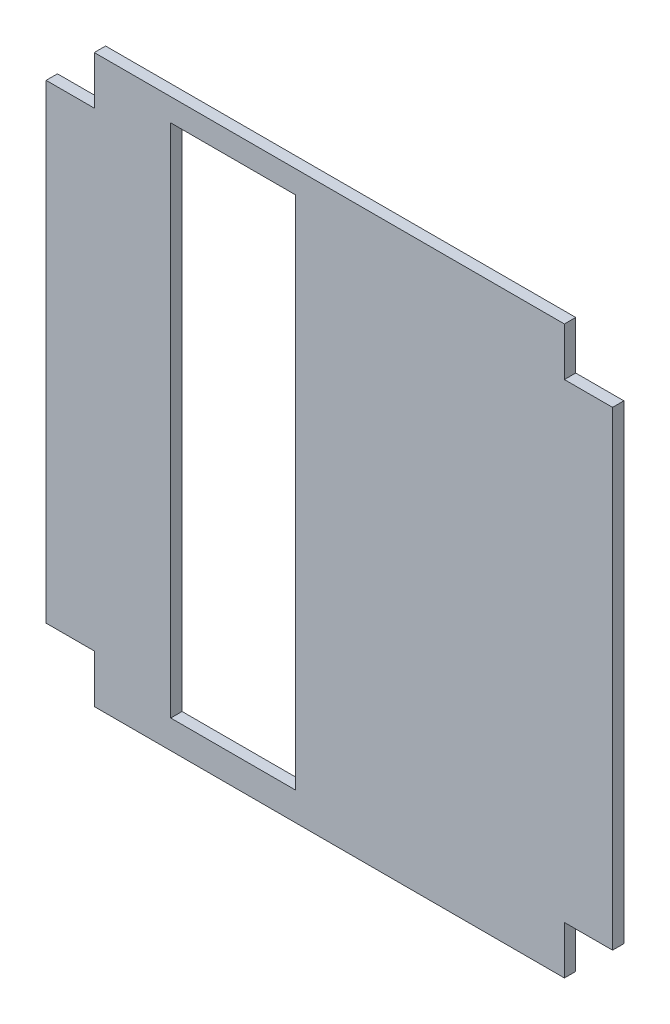
SolidWorks part; units mm, degrees
ref_plane "Front Plane" through (0, 0, 0) normal (0, 0, 1) x (1, 0, 0)
ref_plane "Top Plane" through (0, 0, 0) normal (0, 1, 0) x (1, 0, 0)
ref_plane "Right Plane" through (0, 0, 0) normal (1, 0, 0) x (0, 0, -1)
sketch "Sketch1" plane through (0, 0, 0) normal (0, 0, 1) x (1, 0, 0)
  line L55 (-99, 90.5) -> (-99, 7.5)
  line L58 (-7.5, 99) -> (-90.5, 99)
  line L61 (1, 90.5) -> (1, 7.5)
  line L64 (-90.5, -1) -> (-7.5, -1)
  line L90 (-7.5, 99) -> (-7.5, 90.5)
  line L91 (-7.5, 90.5) -> (1, 90.5)
  line L97 (-90.5, 90.5) -> (-90.5, 99)
  line L98 (-99, 90.5) -> (-90.5, 90.5)
  line L104 (-90.5, 7.5) -> (-99, 7.5)
  line L105 (-90.5, -1) -> (-90.5, 7.5)
  line L107 (-7.5, 7.5) -> (-7.5, -1)
  line L110 (1, 7.5) -> (-7.5, 7.5)
  line L128 (-77, 4) -> (-55, 4)
  line L129 (-55, 95) -> (-77, 95)
  line L130 (-55, 4) -> (-55, 95)
  line L131 (-77, 95) -> (-77, 4)
extrude "Boss-Extrude1" add sketch "Sketch1" along normal blind 2 contours L55 L104 L105 L64 L107 L110 L61 L91 L90 L58 L97 L98
extrude "Cut-Extrude1" cut sketch "Sketch1<5>" along normal through all contours L130 L129 L131 L128
sketch "Sketch1<5>" plane through (0, 0, 0) normal (0, 0, 1) x (1, 0, 0) same geometry as "Sketch1"
